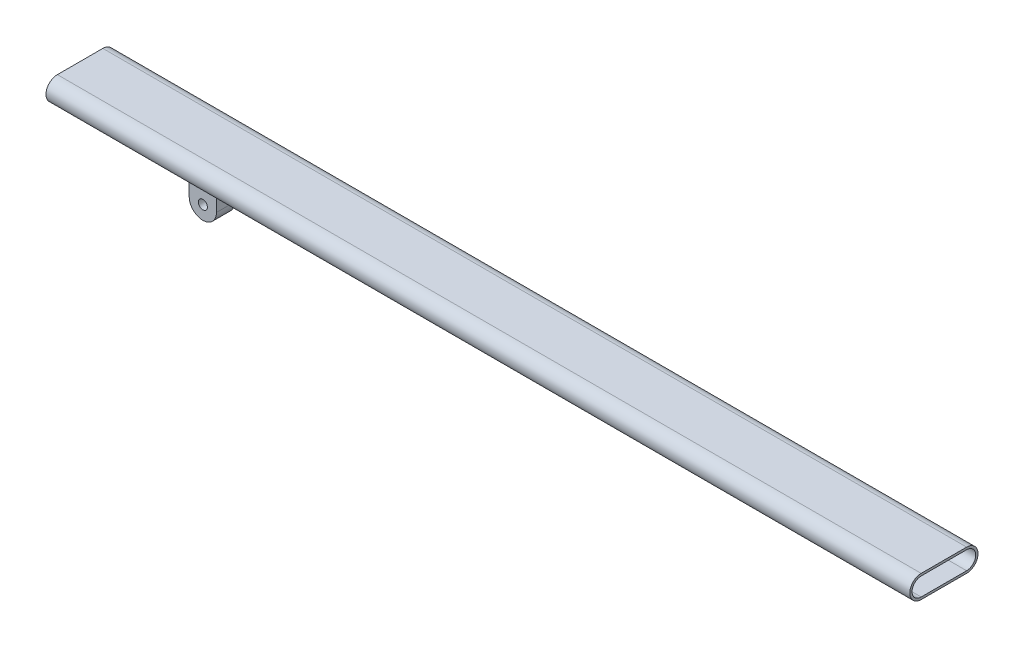
SolidWorks part; units mm, degrees
ref_plane "前视基准面" through (0, 0, 0) normal (0, 0, 1) x (1, 0, 0)
ref_plane "上视基准面" through (0, 0, 0) normal (0, 1, 0) x (1, 0, 0)
ref_plane "右视基准面" through (0, 0, 0) normal (1, 0, 0) x (0, 0, -1)
sketch "草图1" plane through (0, 0, 0) normal (1, 0, 0) x (0, 0, -1)
  line L0 (10, 0) -> (-10, 0) construction
  line L1 (10, -5) -> (-10, -5)
  line L2 (10, 5) -> (-10, 5)
  arc A0 (10, -5) -> (10, 5) centre (10, 0) ccw
  arc A1 (-10, 5) -> (-10, -5) centre (-10, 0) ccw
  point P2 (0, 0)
  point P8 (-15, 0)
  point P9 (15, 0)
  dimension "D1" = 30
  dimension "D2" = 10
extrude "凸台-拉伸1" add sketch "草图1" along normal blind 380
sketch "草图2" plane through (0, -5, 0) normal (0, -1, 0) x (1, 0, 0)
  line L0 (73, 0) -> (43, 0) construction
  line L1 (73, -5) -> (43, -5)
  line L2 (73, 5) -> (43, 5)
  arc A0 (73, -5) -> (73, 5) centre (73, 0) ccw
  arc A1 (43, 5) -> (43, -5) centre (43, 0) ccw
  point P2 (58, 0)
  point P8 (38, 0)
  point P9 (78, 0)
  dimension "D1" = 58
  dimension "D2" = 40
  dimension "D3" = 10
extrude "切除-拉伸1" cut sketch "草图2" against normal blind 0.5
sketch "草图3" plane through (0, -4.5, 0) normal (0, -1, 0) x (1, 0, 0)
  line L0 (15.6116, 0) -> (118.021, 0) construction
  line L2 (64, -4) -> (52, -4)
  line L3 (64, -4) -> (64, 4)
  line L4 (64, 4) -> (52, 4)
  line L5 (52, -4) -> (52, 4)
  line L6 (64, -4) -> (52, 4) construction
  line L7 (64, 4) -> (52, -4) construction
  point P3 (58, 0)
  dimension "D1" = 12
  dimension "D2" = 8
extrude "凸台-拉伸2" add sketch "草图3" along normal blind 20
fillet "圆角1" radius 6 2 edges at (64, -24.5, 0) (52, -24.5, 0)
sketch "草图4" plane through (0, 0, 0) normal (-1, 0, 0) x (0, 0, 1)
  line L4 (-10, -4) -> (10, -4)
  line L5 (10, 4) -> (-10, 4)
  line L6 (-10, -4) -> (10, -4)
  line L7 (10, 4) -> (-10, 4)
  arc A4 (-10, 4) -> (-10, -4) centre (-10, 0) ccw
  arc A5 (10, -4) -> (10, 4) centre (10, 0) ccw
  arc A6 (-10, 4) -> (-10, -4) centre (-10, 0) ccw
  arc A7 (10, -4) -> (10, 4) centre (10, 0) ccw
  dimension "D1" = 1
extrude "切除-拉伸2" cut sketch "草图4" against normal through all both and the other way through all
sketch "草图5" plane through (0, -5, 0) normal (0, -1, 0) x (1, 0, 0)
  line L0 (363, 0) -> (177, 0) construction
  line L1 (363, -8) -> (177, -8)
  line L2 (363, 8) -> (177, 8)
  line L3 (380, 10) -> (380, -10) construction
  arc A0 (363, -8) -> (363, 8) centre (363, 0) ccw
  arc A1 (177, 8) -> (177, -8) centre (177, 0) ccw
  point P2 (270, 0)
  point P8 (371, 0)
  point P9 (169, 0)
  dimension "D1" = 202
  dimension "D2" = 9
  dimension "D3" = 16
extrude "切除-拉伸3" cut sketch "草图5" against normal up to surface (9 mm away) up to face at (190, 4, 0)
sketch "草图6" plane through (0, 0, 4) normal (0, 0, 1) x (1, 0, 0)
  circle A0 centre (58, -18.5) radius 2
  dimension "D1" = 4
extrude "切除-拉伸4" cut sketch "草图6" against normal through all both and the other way through all
hole_wizard "#1-64 螺纹孔1" positions "草图26" profile "草图25" tap size "#1-64" standard "ANSI Inch"
sketch "草图26" plane through (0, -4.5, 0) normal (0, -1, 0) x (-1, 0, 0)
  point P0 (-43, 0)
  point P3 (-73, 0)
sketch "草图25" plane through (43, -4.5, 0) normal (1, 0, 0) x (0, 0, -1)
  line L0 (0, 0) -> (0, 6.144)
  line L1 (0, 6.144) -> (0.7556, 5.69)
  line L2 (0.7556, 5.69) -> (0.7556, 0)
  line L5 (0.7556, 0) -> (0, 0)
  line L10 (0, 6.144) -> (-0.7557, 5.69) construction
  line L11 (0, -6.35) -> (0, 107.95) construction
  dimension "螺纹孔钻头直径" = 1.5113
  dimension "螺纹孔钻头深度" = 5.69
  dimension "导头角度" = 118
cosmetic thread "孔螺蚊线1" parameters "D1"=3.71, "D2"=1.8542
cosmetic thread "孔螺蚊线2" parameters "D1"=3.71, "D2"=1.8542
